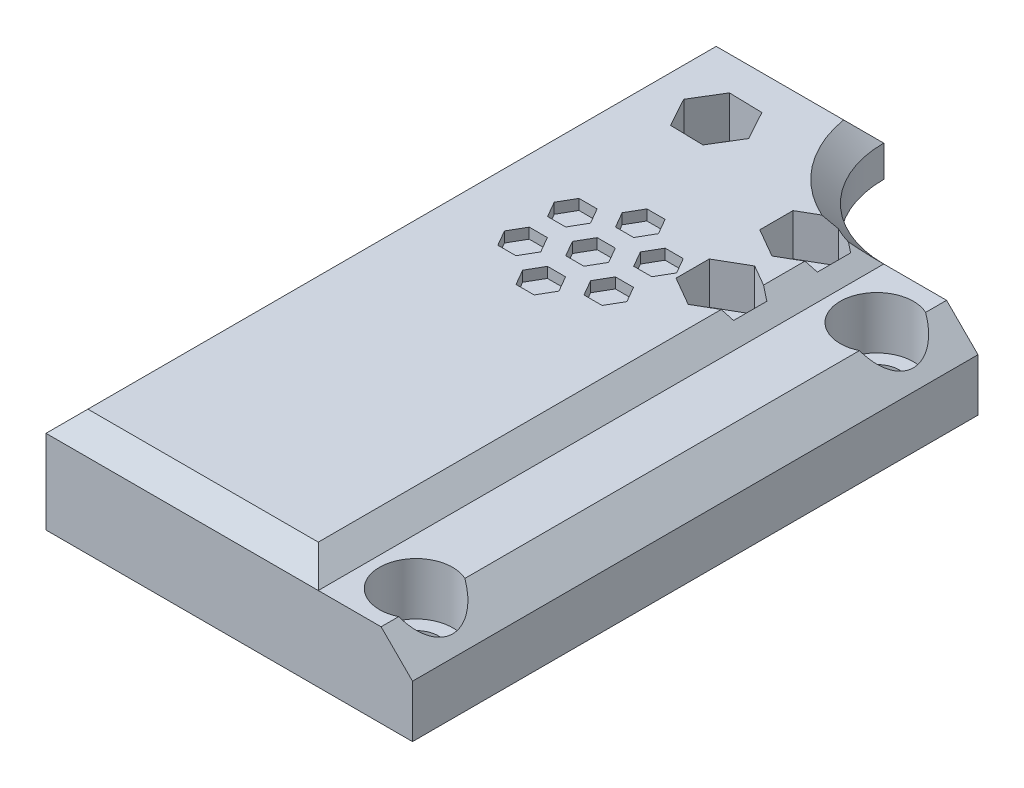
SolidWorks part; units mm, degrees
ref_plane "Front Plane" through (0, 0, 0) normal (0, 0, 1) x (1, 0, 0)
ref_plane "Top Plane" through (0, 0, 0) normal (0, 1, 0) x (1, 0, 0)
ref_plane "Right Plane" through (0, 0, 0) normal (1, 0, 0) x (0, 0, -1)
sketch "Sketch1" plane through (0, 0, 0) normal (0, 1, 0) x (1, 0, 0)
  line L1 (0, 0) -> (26, 0)
  line L2 (0, 0) -> (0, 39)
  line L3 (0, 39) -> (26, 39)
  line L4 (26, 0) -> (26, 39)
  dimension "D1" = 39
  dimension "D2" = 26
extrude "Boss-Extrude1" add sketch "Sketch1" along normal blind 10
sketch "Sketch2" plane through (0, 0, -39) normal (0, 0, -1) x (-1, 0, 0)
  line L0 (-26, 10) -> (-26, 0) construction
  line L1 (-26, 5) -> (0, 5)
  line L2 (-26, 5) -> (-26, 10)
  line L3 (-26, 10) -> (0, 10)
  line L4 (0, 5) -> (0, 10)
extrude "Boss-Extrude2" add sketch "Sketch2" along normal blind 25
sketch "Sketch3" plane through (0, 10, 0) normal (0, 1, 0) x (1, 0, 0)
  line L0 (0, 64) -> (0, 0) construction
  line L1 (0, 64) -> (26, 64) construction
  line L2 (0, 54) -> (0, 64)
  line L3 (0, 64) -> (10, 64)
  arc A0 (0, 54) -> (10, 64) centre (0, 64) ccw
  dimension "D1" = 10
extrude "Cut-Extrude1" cut sketch "Sketch3" against normal up to next
chamfer "Chamfer1" distance 2 angle 45 5 edges at (18, 10, -64) (7.0711, 10, -56.9289) (0, 10, -27) (26, 10, -32) (13, 10, 0)
sketch "Sketch4" plane through (0, 0, 0) normal (-1, 0, 0) x (0, 0, 1)
  line L1 (-54, 8) -> (0, 8)
  line L2 (-54, 8) -> (-54, 0)
  line L3 (-54, 0) -> (0, 0)
  line L4 (0, 8) -> (0, 0)
extrude "Boss-Extrude3" add sketch "Sketch4" along normal blind 9
sketch "Sketch5" plane through (0, 8, 0) normal (0, 1, 0) x (1, 0, 0)
  line L0 (-4.5, 48.8375) -> (-4.5, 4.8375) construction
  line L1 (-9, 0) -> (-9, 54) construction
  circle A0 centre (-4.5, 48.8375) radius 2.15
  circle A1 centre (-4.5, 4.8375) radius 2.15
  dimension "D1" = 4.3
  dimension "D2" = 4.5
  dimension "D3" = 44
extrude "Cut-Extrude2" cut sketch "Sketch5" against normal up to next
sketch "Sketch6" plane through (0, 8, 0) normal (0, 1, 0) x (1, 0, 0)
  circle A0 centre (-4.5, 48.8375) radius 3.5
  circle A1 centre (-4.5, 4.8375) radius 3.5
  dimension "D1" = 7
extrude "Cut-Extrude3" cut sketch "Sketch6" against normal blind 5
chamfer "Chamfer3" distance 3 angle 45 1 edges at (-9, 8, -27)
sketch "Sketch10" plane through (0, 10, 0) normal (0, 1, 0) x (1, 0, 0)
  line L0 (24, 2) -> (24, 62) construction
  line L1 (14.7321, 39) -> (13.866, 40.5)
  line L2 (13.866, 40.5) -> (12.134, 40.5)
  line L3 (12.134, 40.5) -> (11.2679, 39)
  line L4 (11.2679, 39) -> (12.134, 37.5)
  line L5 (12.134, 37.5) -> (13.866, 37.5)
  line L6 (13.866, 37.5) -> (14.7321, 39)
  line L7 (14.7321, 43.75) -> (13.866, 45.25)
  line L8 (13.866, 45.25) -> (12.134, 45.25)
  line L9 (12.134, 45.25) -> (11.2679, 43.75)
  line L10 (11.2679, 43.75) -> (12.134, 42.25)
  line L11 (12.134, 42.25) -> (13.866, 42.25)
  line L12 (13.866, 42.25) -> (14.7321, 43.75)
  line L13 (0, 0) -> (13, 39) construction
  line L14 (13, 39) -> (13, 0) construction
  line L16 (13, 0) -> (0, 0) construction
  line L17 (0, 0) -> (13, 0) construction
  line L19 (2, 2) -> (24, 2) construction
  line L20 (17.9796, 39.875) -> (18.8457, 41.375)
  line L21 (18.8457, 41.375) -> (17.9796, 42.875)
  line L22 (17.9796, 42.875) -> (16.2476, 42.875)
  line L23 (16.2476, 42.875) -> (15.3816, 41.375)
  line L24 (15.3816, 41.375) -> (16.2476, 39.875)
  line L25 (16.2476, 39.875) -> (17.9796, 39.875)
  line L26 (16.2476, 35.125) -> (17.9796, 35.125)
  line L27 (17.9796, 35.125) -> (18.8457, 36.625)
  line L28 (18.8457, 36.625) -> (17.9796, 38.125)
  line L29 (17.9796, 38.125) -> (16.2476, 38.125)
  line L30 (16.2476, 38.125) -> (15.3816, 36.625)
  line L31 (15.3816, 36.625) -> (16.2476, 35.125)
  line L32 (11.2679, 34.25) -> (12.134, 32.75)
  line L33 (12.134, 32.75) -> (13.866, 32.75)
  line L34 (13.866, 32.75) -> (14.7321, 34.25)
  line L35 (14.7321, 34.25) -> (13.866, 35.75)
  line L36 (13.866, 35.75) -> (12.134, 35.75)
  line L37 (12.134, 35.75) -> (11.2679, 34.25)
  line L38 (8.0204, 38.125) -> (7.1543, 36.625)
  line L39 (7.1543, 36.625) -> (8.0204, 35.125)
  line L40 (8.0204, 35.125) -> (9.7524, 35.125)
  line L41 (9.7524, 35.125) -> (10.6184, 36.625)
  line L42 (10.6184, 36.625) -> (9.7524, 38.125)
  line L43 (9.7524, 38.125) -> (8.0204, 38.125)
  line L44 (9.7524, 42.875) -> (8.0204, 42.875)
  line L45 (8.0204, 42.875) -> (7.1543, 41.375)
  line L46 (7.1543, 41.375) -> (8.0204, 39.875)
  line L47 (8.0204, 39.875) -> (9.7524, 39.875)
  line L48 (9.7524, 39.875) -> (10.6184, 41.375)
  line L49 (10.6184, 41.375) -> (9.7524, 42.875)
  circle A0 centre (13, 39) radius 1.5 construction
  circle A1 centre (13, 43.75) radius 1.5 construction
  point P55 (13, 39)
  dimension "D1" = 3
  dimension "D2" = 4.75
  dimension "D3" = 11
  dimension "D4" = 13
  dimension "D5" = 37
  dimension "D6" = 6
extrude "Cut-Extrude5" cut sketch "Sketch10" against normal blind 1
sketch "Sketch11" plane through (0, 10, 0) normal (0, 1, 0) x (1, 0, 0)
  line L0 (18, 64) -> (18, 0) construction
  line L1 (6.75, 44.0877) -> (4, 45.6754)
  line L2 (4, 45.6754) -> (1.25, 44.0877)
  line L3 (1.25, 44.0877) -> (1.25, 40.9123)
  line L4 (1.25, 40.9123) -> (4, 39.3246)
  line L5 (4, 39.3246) -> (6.75, 40.9123)
  line L6 (6.75, 40.9123) -> (6.75, 44.0877)
  line L7 (6.75, 52.0877) -> (4, 53.6754)
  line L8 (4, 53.6754) -> (1.25, 52.0877)
  line L9 (1.25, 52.0877) -> (1.25, 48.9123)
  line L10 (1.25, 48.9123) -> (4, 47.3246)
  line L11 (4, 47.3246) -> (6.75, 48.9123)
  line L12 (6.75, 48.9123) -> (6.75, 52.0877)
  line L13 (21.1745, 56.0763) -> (19.5211, 58.7874)
  line L14 (19.5211, 58.7874) -> (16.3466, 58.711)
  line L15 (16.3466, 58.711) -> (14.8255, 55.9237)
  line L16 (14.8255, 55.9237) -> (16.4789, 53.2126)
  line L17 (16.4789, 53.2126) -> (19.6534, 53.289)
  line L18 (19.6534, 53.289) -> (21.1745, 56.0763)
  line L19 (10, 64) -> (26, 64) construction
  line L20 (26, 0) -> (0, 0) construction
  line L21 (4, 50.5) -> (4, 42.5) construction
  line L22 (0, 0) -> (0, 54) construction
  line L25 (2, 52.1678) -> (2, 2) construction
  circle A0 centre (4, 42.5) radius 2.75 construction
  circle A1 centre (4, 50.5) radius 2.75 construction
  circle A2 centre (18, 56) radius 2.75 construction
  dimension "D1" = 5.5
  dimension "D2" = 4
  dimension "D3" = 8
  dimension "D4" = 3.5
  dimension "D5" = 17
extrude "Cut-Extrude6" cut sketch "Sketch11" against normal blind 4
sketch "Sketch12" plane through (0, 10, 0) normal (0, 1, 0) x (1, 0, 0)
  line L0 (4, 53.6754) -> (4, 47.3246) construction
  line L2 (4, 45.6754) -> (4, 39.3246) construction
  line L4 (19.6534, 53.289) -> (16.3466, 58.711) construction
  circle A0 centre (4, 50.5) radius 1.65
  circle A1 centre (4, 42.5) radius 1.65
  circle A2 centre (18, 56) radius 1.65
  dimension "D1" = 3.3
extrude "Cut-Extrude7" cut sketch "Sketch12" against normal up to next
sketch "Sketch14" plane through (0, 0, 0) normal (0, -1, 0) x (1, 0, 0)
  line L0 (26, 0) -> (26, -39) construction
  line L1 (12.75, -17) -> (24.75, -17)
  line L2 (12.75, -17) -> (12.75, -29)
  line L3 (12.75, -29) -> (24.75, -29)
  line L4 (24.75, -17) -> (24.75, -29)
  line L5 (-9, 0) -> (26, 0) construction
  dimension "D1" = 1.25
  dimension "D2" = 17
  dimension "D3" = 12
  dimension "D4" = 12
extrude "Cut-Extrude9" cut sketch "Sketch14" against normal blind 7
ref_plane "Plane1" through (26, 0, 0) normal (1, 0, 0) x (0, 0, -1)
mirror "Mirror3" about plane through (26, 0, 0) normal (1, 0, 0) of bodies 112
sketch "Sketch15" plane through (0, 0, 0) normal (0, 0, 1) x (1, 0, 0)
  line L0 (-9, 0) -> (61, 0) construction
  line L1 (26, 0) -> (-11.4671, 0)
  line L2 (26, 0) -> (26, 12.7195)
  line L3 (26, 12.7195) -> (-11.4671, 12.7195)
  line L4 (-11.4671, 0) -> (-11.4671, 12.7195)
extrude "Cut-Extrude10" cut sketch "Sketch15" against normal through all
sketch "Sketch16" plane through (0, 0, 0) normal (0, -1, 0) x (1, 0, 0)
  line L0 (27.25, -17) -> (39.25, -17) construction
  line L1 (39.25, -29) -> (44.25, -29)
  line L2 (39.25, -29) -> (39.25, -17)
  line L3 (39.25, -17) -> (44.25, -17)
  line L4 (44.25, -29) -> (44.25, -17)
  dimension "D1" = 5
extrude "Cut-Extrude11" cut sketch "Sketch16" against normal up to surface (7 mm away) up to face at (33.25, 7, -23)
